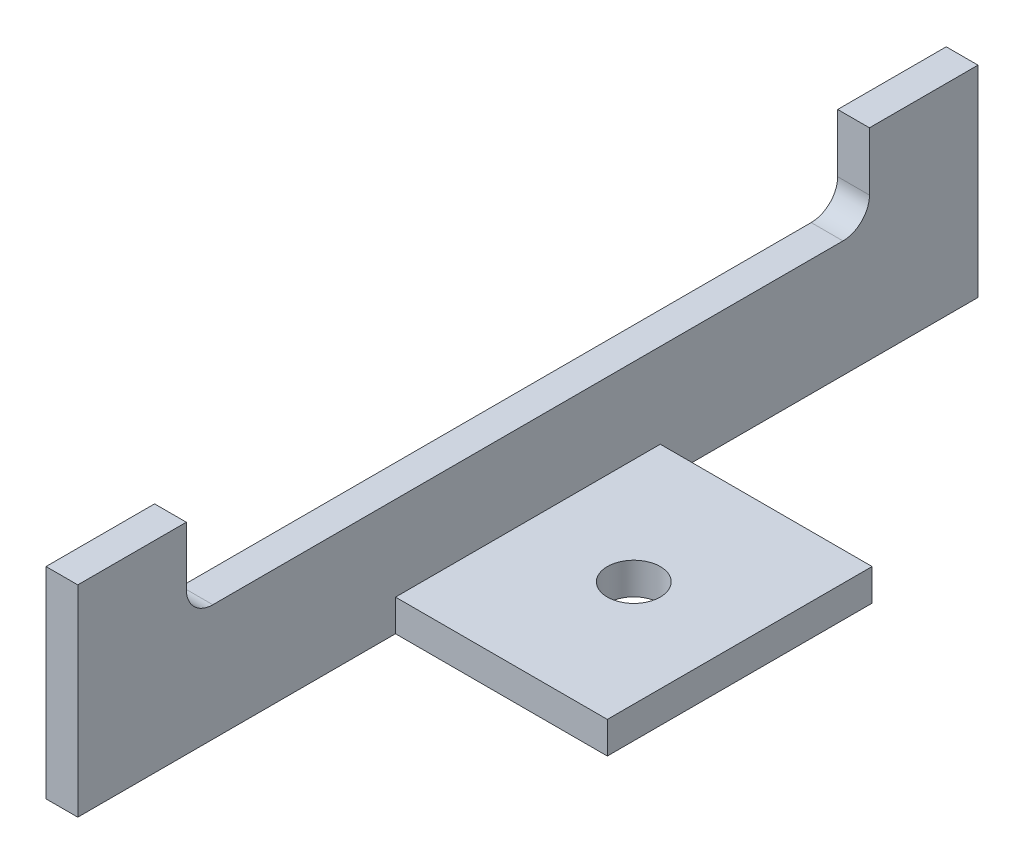
SolidWorks part; units mm, degrees
material "1060-H16"
ref_plane "Alzado" through (0, 0, 0) normal (0, 0, 1) x (1, 0, 0)
ref_plane "Planta" through (0, 0, 0) normal (0, 1, 0) x (1, 0, 0)
ref_plane "Vista lateral" through (0, 0, 0) normal (1, 0, 0) x (0, 0, -1)
sketch "Croquis1" plane through (0, 0, 0) normal (0, 0, 1) x (1, 0, 0)
  line L0 (0, 0) -> (0, 50)
  line L1 (0, 0) -> (50, 0)
  line L2 (6, 6) -> (50, 6)
  line L3 (6, 6) -> (6, 50)
  line L4 (0, 50) -> (6, 50)
  line L5 (50, 6) -> (50, 0)
  dimension "D2" = 50
  dimension "D1" = 6
extrude "Saliente-Extruir1" add sketch "Croquis1" along normal blind 170
sketch "Croquis2" plane through (0, 0, 0) normal (-1, 0, 0) x (0, 0, 1)
  line L0 (170, 35) -> (0, 35) construction
  line L1 (170, 50) -> (170, 0) construction
  line L2 (0, 50) -> (0, 0) construction
  line L3 (170, 6) -> (0, 6) construction
  line L4 (170, 6) -> (0, 6) construction
  line L5 (85, 6) -> (85, 50) construction
  line L6 (170, 50) -> (0, 50) construction
  line L7 (112.5, 22) -> (112.5, 50)
  line L8 (112.5, 78) -> (57.5, 78) construction
  line L9 (112.5, 78) -> (112.5, 22) construction
  line L10 (112.5, 22) -> (57.5, 22)
  line L11 (57.5, 78) -> (57.5, 22) construction
  line L12 (112.5, 78) -> (57.5, 22) construction
  line L13 (112.5, 22) -> (57.5, 78) construction
  line L14 (57.5, 22) -> (57.5, 50)
  line L15 (57.5, 50) -> (112.5, 50)
  line L16 (149.5, 35) -> (149.5, 50)
  line L17 (130.5, 35) -> (130.5, 50)
  line L18 (130.5, 50) -> (149.5, 50)
  line L19 (39.5, 35) -> (39.5, 50)
  line L20 (20.5, 35) -> (20.5, 50)
  line L21 (39.5, 50) -> (20.5, 50)
  line L22 (170, 0) -> (0, 0) construction
  circle A0 centre (140, 35) radius 9.5 construction
  circle A1 centre (30, 35) radius 9.5 construction
  arc A2 (149.5, 35) -> (130.5, 35) centre (140, 35) cw
  arc A3 (39.5, 35) -> (20.5, 35) centre (30, 35) cw
  dimension "D2" = 19
  dimension "D1" = 35
  dimension "D3" = 55
  dimension "D4" = 55
  dimension "D5" = 22
  dimension "D6" = 55
  dimension "D7" = 20.5
  dimension "D8" = 20.5
extrude "Cortar-Extruir1" cut sketch "Croquis2" against normal up to surface (6 mm away) up to face at (6, 28, 85)
sketch "Croquis3" plane through (0, 0, 0) normal (0, -1, 0) x (1, 0, 0)
  line L0 (0, 85) -> (50, 85) construction
  line L1 (0, 170) -> (0, 0) construction
  line L2 (50, 170) -> (50, 0) construction
  line L3 (6, 170) -> (6, 0) construction
  line L4 (50, 0) -> (6, 0)
  line L5 (50, 0) -> (50, 60)
  line L6 (50, 60) -> (6, 60)
  line L7 (6, 0) -> (6, 60)
  line L8 (6, 170) -> (6, 0) construction
  line L9 (50, 110) -> (6, 110)
  line L10 (6, 170) -> (6, 110)
  line L11 (50, 170) -> (6, 170)
  line L12 (50, 170) -> (50, 110)
  line M5 (0, 0) -> (50, 0)
  line M6 (50, 0) -> (50, 170)
  line M7 (50, 170) -> (0, 170)
  dimension "D1" = 60
extrude "Cortar-Extruir2" cut sketch "Croquis3" against normal up to surface (6 mm away) contours L10 L9 M7 M6 | L7 L6 M5 M6 region at (28, 0, 140) region at (28, 0, 30) up to face at (28, 6, 85)
sketch "Croquis4" plane through (0, 0, 0) normal (0, -1, 0) x (1, 0, 0)
  line L0 (46, 60) -> (46, 110)
  line L1 (50, 60) -> (6, 60) construction
  line L2 (50, 110) -> (6, 110) construction
  line L3 (46, 110) -> (50, 110)
  line L4 (50, 110) -> (50, 60)
  line L5 (50, 60) -> (46, 60)
  dimension "D1" = 4
extrude "Cortar-Extruir3" cut sketch "Croquis4" against normal blind 10
sketch "Croquis5" plane through (0, 0, 0) normal (-1, 0, 0) x (0, 0, 1)
  line L0 (170, 38) -> (0, 38) construction
  line L1 (170, 50) -> (170, 0) construction
  line L2 (0, 50) -> (0, 0) construction
  line L3 (170, 50) -> (149.5, 50) construction
  line L4 (170, 38) -> (149.5, 38)
  line L5 (149.5, 38) -> (149.5, 50)
  line L6 (149.5, 50) -> (170, 50)
  line L7 (170, 50) -> (170, 38)
  line L8 (149.5, 35) -> (149.5, 50) construction
  line L9 (112.5, 50) -> (112.5, 38)
  line L10 (112.5, 22) -> (112.5, 50) construction
  line L11 (112.5, 38) -> (130.5, 38)
  line L12 (130.5, 50) -> (130.5, 35) construction
  line L13 (130.5, 38) -> (130.5, 50)
  line L14 (130.5, 50) -> (112.5, 50)
  line L15 (85, 22) -> (85, 38) construction
  line L16 (57.5, 22) -> (112.5, 22) construction
  line L17 (39.5, 38) -> (39.5, 50)
  line L18 (57.5, 38) -> (39.5, 38)
  line L19 (57.5, 50) -> (57.5, 38)
  line L20 (39.5, 50) -> (57.5, 50)
  line L21 (20.5, 50) -> (0, 50)
  line L22 (20.5, 38) -> (20.5, 50)
  line L23 (0, 38) -> (20.5, 38)
  line L24 (0, 50) -> (0, 38)
  dimension "D1" = 12
extrude "Cortar-Extruir4" cut sketch "Croquis5" against normal up to surface (6 mm away) up to face at (6, 28.85, 85)
sketch "Croquis6" plane through (0, 0, 0) normal (-1, 0, 0) x (0, 0, 1)
  line L0 (149.5, 38) -> (149.5, 22)
  line L1 (149.5, 22) -> (20.5, 22)
  line L2 (20.5, 22) -> (20.5, 38)
  line L3 (170, 0) -> (0, 0) construction
  line L4 (149.5, 38) -> (20.5, 38)
  dimension "D1" = 22
extrude "Cortar-Extruir5" cut sketch "Croquis6" against normal up to surface (6 mm away) up to face at (6, 24.05, 85)
sketch "Croquis7" plane through (0, 0, 0) normal (0, -1, 0) x (1, 0, 0)
  circle A0 centre (26, 85) radius 5 construction
  circle A1 centre (26, 85) radius 5
extrude "Cortar-Extruir6" cut sketch "Croquis7" against normal up to surface (6 mm away) up to face at (26, 6, 85)
fillet "Redondeo1" radius 5 2 edges at (3, 22, 149.5) (3, 22, 20.5)
